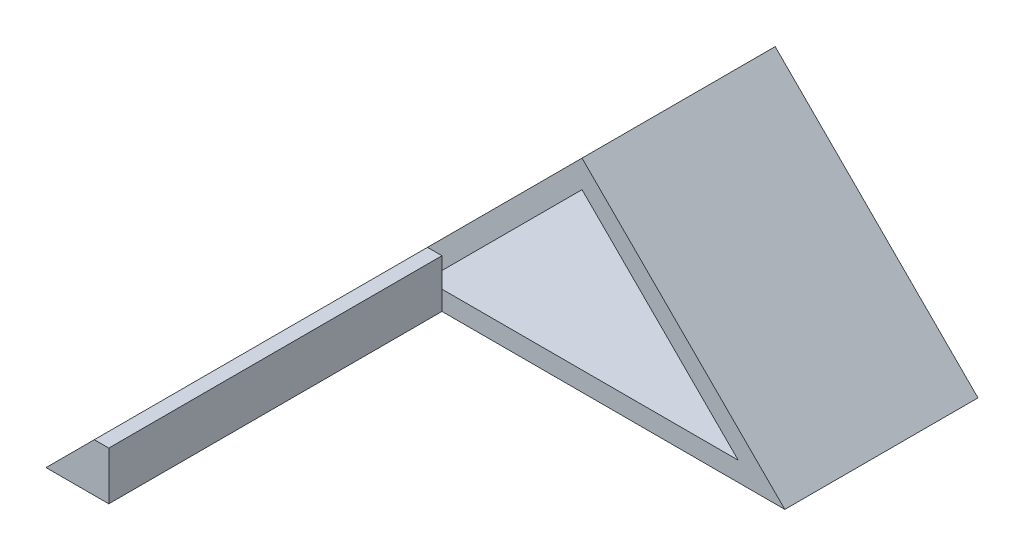
SolidWorks part; units mm, degrees
ref_plane "Front Plane" through (0, 0, 0) normal (0, 0, 1) x (1, 0, 0)
ref_plane "Top Plane" through (0, 0, 0) normal (0, 1, 0) x (1, 0, 0)
ref_plane "Right Plane" through (0, 0, 0) normal (1, 0, 0) x (0, 0, -1)
sketch "Sketch1" plane through (0, 0, 0) normal (0, 0, 1) x (1, 0, 0)
  line L1 (0, 0) -> (-42, -42)
  line L2 (0, -1000.3549) -> (0, 48999.6451) construction
  line L3 (-32.3431, -38) -> (0, -5.6569)
  line L4 (32.3431, -38) -> (0, -5.6569)
  line L5 (0, 0) -> (42, -42)
  line L7 (-42, -42) -> (42, -42)
  line L8 (-32.3431, -38) -> (32.3431, -38)
  line L9 (-34, -34) -> (34, -34) construction
  dimension "D1" = 90
  dimension "D2" = 4
  dimension "D3" = 4
  dimension "D4" = 68
  dimension "D5" = 8
extrude "Boss-Extrude1" add sketch "Sketch1" along normal mid plane 40
sketch "Sketch2" plane through (0, 0, 0) normal (1, 0, 0) x (0, 0, -1)
  line L0 (0, -1034.3624) -> (0, 48965.6376) construction
  line L1 (-20, -42) -> (20, -42) construction
  line L2 (-3.5, -42) -> (-3.5, -65.5)
  line L3 (-3.5, -65.5) -> (-9, -65.5)
  line L4 (-9, -65.5) -> (-9, -69)
  line L5 (-9, -69) -> (9, -69)
  line L6 (9, -65.5) -> (9, -69)
  line L7 (3.5, -65.5) -> (9, -65.5)
  line L8 (3.5, -42) -> (3.5, -65.5)
  line L9 (3.5, -42) -> (-3.5, -42)
  point P5 (0, -42)
  dimension "D1" = 7
  dimension "D2" = 3.5
  dimension "D3" = 27
  dimension "D4" = 18
extrude "Boss-Extrude2" [suppressed] add sketch "Sketch2" along normal blind 6 from vertex starting at point (-42, -42, 0)
sketch "Sketch4" [suppressed] plane through (0, 0, 0) normal (1, 0, 0) x (0, 0, -1)
  line L0 (-20, -38.4859) -> (20, -38.4859) construction
  line L1 (3.5, -38.4859) -> (13.5, -38.4859)
  line L2 (3.5, -38.4859) -> (3.5, -65.4859)
  line L3 (3.5, -65.4859) -> (13.5, -65.4859)
  line L4 (13.5, -38.4859) -> (13.5, -65.4859)
  line L5 (-9, -65.4859) -> (9, -65.4859) construction
  line L7 (-11, -38.4859) -> (-18.5, -38.4859)
  line L8 (-11, -38.4859) -> (-11, -65.4859)
  line L9 (-11, -65.4859) -> (-18.5, -65.4859)
  line L10 (-18.5, -38.4859) -> (-18.5, -65.4859)
  line L11 (-9, -61.9859) -> (-9, -65.4859) construction
  dimension "D1" = 10
  dimension "D2" = 2
  dimension "D3" = 7.5
extrude "Boss-Extrude3" [suppressed] add sketch "Sketch4" against normal blind 6 from vertex starting at point (42, -42, 20)
sketch "Sketch5" plane through (0, 0, 20) normal (0, 0, 1) x (1, 0, 0)
  line L0 (-42, -42) -> (-32, -32)
  line L1 (0, 0) -> (-42, -42) construction
  line L2 (-32, -32) -> (-29, -32)
  line L3 (-29, -32) -> (-29, -42)
  line L4 (-42, -42) -> (42, -42) construction
  line L5 (-29, -42) -> (-42, -42)
  point P5 (-30, -32.7198)
  dimension "D1" = 13
  dimension "D2" = 3
extrude "Boss-Extrude4" add sketch "Sketch5" along normal blind 69
